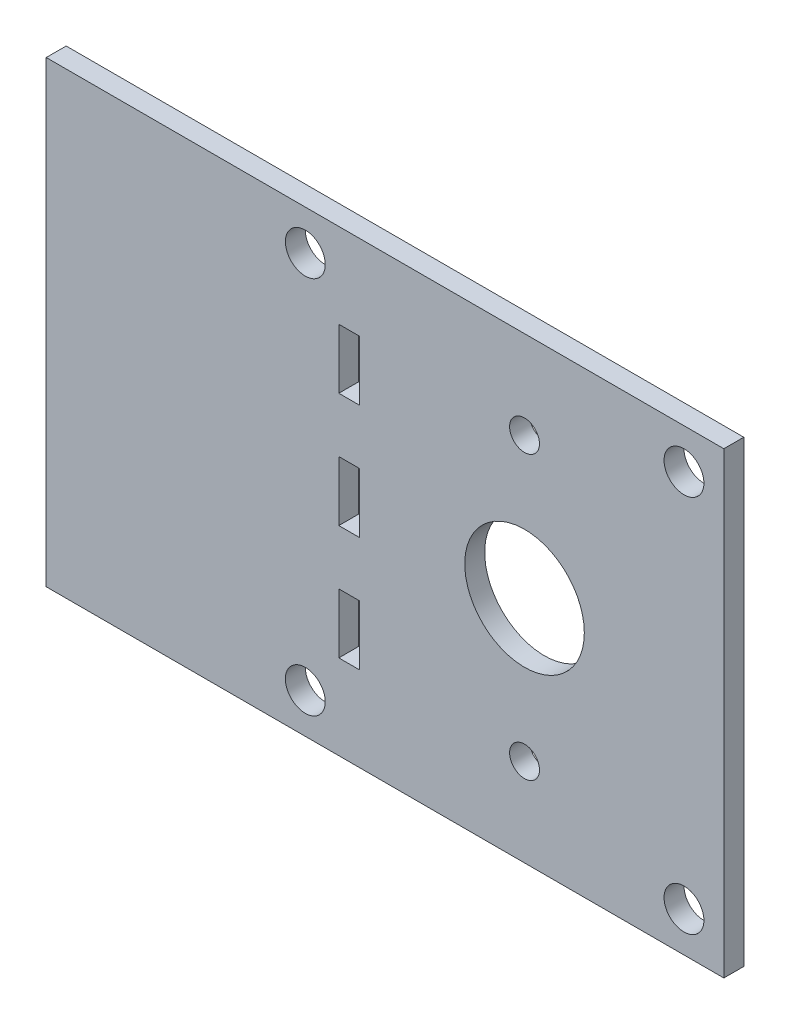
SolidWorks part; units mm, degrees
ref_plane "Front Plane" through (0, 0, 0) normal (0, 0, 1) x (1, 0, 0)
ref_plane "Top Plane" through (0, 0, 0) normal (0, 1, 0) x (1, 0, 0)
ref_plane "Right Plane" through (0, 0, 0) normal (1, 0, 0) x (0, 0, -1)
sketch "Sketch1" plane through (0, 0, 0) normal (0, 0, 1) x (1, 0, 0)
  line L0 (0, 73.025) -> (0, -73.025) construction
  line L1 (63.5, 73.025) -> (-152.4, 73.025)
  line L2 (63.5, 73.025) -> (63.5, -73.025)
  line L3 (63.5, -73.025) -> (-152.4, -73.025)
  line L4 (-152.4, 73.025) -> (-152.4, -73.025)
  line L5 (0, 45) -> (0, -45) construction
  line L6 (-55.88, 73.025) -> (-55.88, 36.5125) construction
  line L7 (-59.182, -9.525) -> (-52.578, -9.525)
  line L8 (-59.182, -9.525) -> (-59.182, 9.525)
  line L9 (-59.182, 9.525) -> (-52.578, 9.525)
  line L10 (-52.578, -9.525) -> (-52.578, 9.525)
  line L11 (-59.182, -9.525) -> (-52.578, 9.525) construction
  line L12 (-59.182, 9.525) -> (-52.578, -9.525) construction
  line L13 (-59.182, 46.0375) -> (-52.578, 46.0375)
  line L14 (-59.182, 46.0375) -> (-59.182, 26.9875)
  line L15 (-59.182, 26.9875) -> (-52.578, 26.9875)
  line L16 (-52.578, 46.0375) -> (-52.578, 26.9875)
  line L17 (-59.182, 46.0375) -> (-52.578, 26.9875) construction
  line L18 (-59.182, 26.9875) -> (-52.578, 46.0375) construction
  line L19 (-59.182, -26.9875) -> (-52.578, -26.9875)
  line L20 (-59.182, -26.9875) -> (-59.182, -46.0375)
  line L21 (-59.182, -46.0375) -> (-52.578, -46.0375)
  line L22 (-52.578, -26.9875) -> (-52.578, -46.0375)
  line L23 (-59.182, -26.9875) -> (-52.578, -46.0375) construction
  line L24 (-59.182, -46.0375) -> (-52.578, -26.9875) construction
  line L25 (-55.88, 36.5125) -> (-55.88, 0) construction
  line L26 (-55.88, 0) -> (-55.88, -36.5125) construction
  line L27 (-55.88, -36.5125) -> (-55.88, -73.025) construction
  circle A0 centre (50.8, 60.325) radius 6.35
  circle A1 centre (50.8, -60.325) radius 6.35
  circle A2 centre (0, 0) radius 19.05
  circle A3 centre (0, 45) radius 4.7625
  circle A4 centre (0, -45) radius 4.7625
  circle A5 centre (-69.85, 60.325) radius 6.35
  circle A6 centre (-69.85, -60.325) radius 6.35
  point P0 (0, 0)
  point P14 (0, 0)
  point P19 (0, 0)
  point P24 (-55.88, 36.5125)
  point P28 (-55.88, 0)
  point P34 (-55.88, -36.5125)
  dimension "D2" = 12.7
  dimension "D6" = 38.1
  dimension "D8" = 9.525
  dimension "D1" = 146.05
  dimension "D3" = 12.7
  dimension "D4" = 12.7
  dimension "D5" = 50.8
  dimension "D7" = 90
  dimension "D9" = 12.7
  dimension "D10" = 152.4
  dimension "D11" = 69.85
  dimension "D12" = 19.05
  dimension "D13" = 6.604
  dimension "D14" = 55.88
extrude "Boss-Extrude1" add sketch "Sketch1" along normal mid plane 6.35
